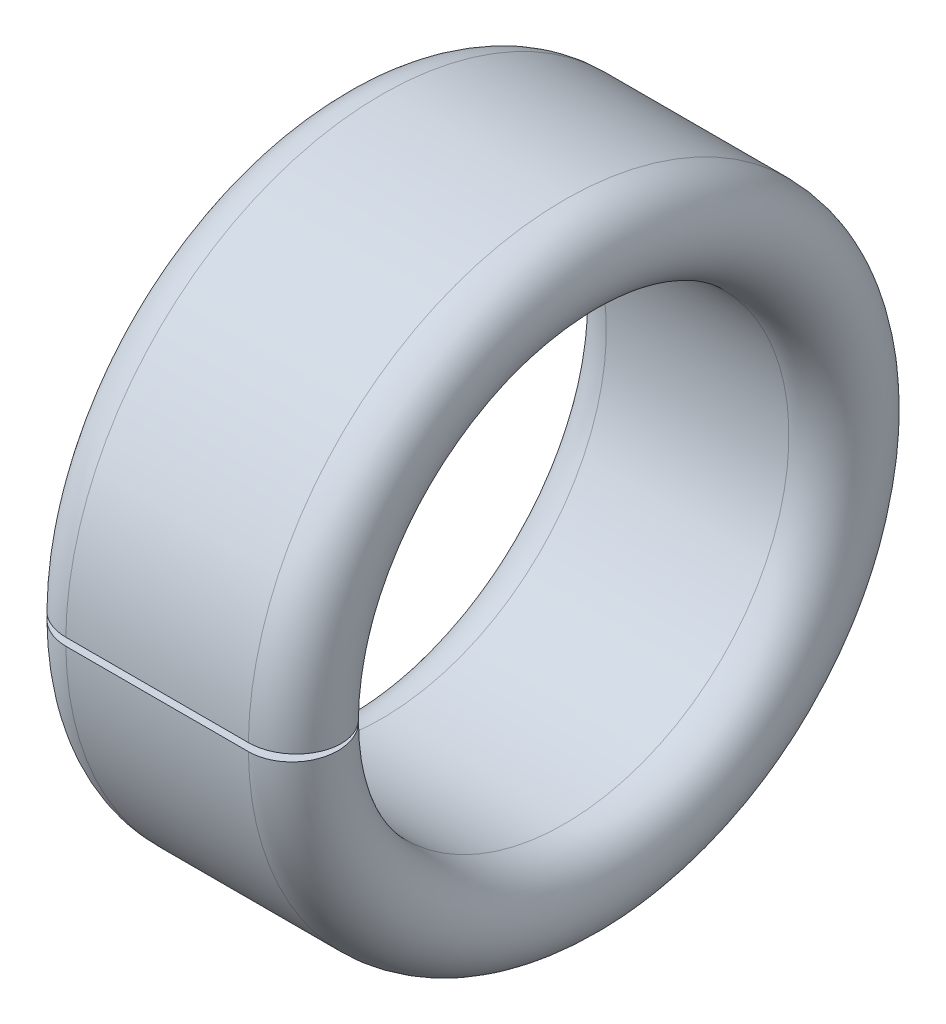
SolidWorks part; units mm, degrees
ref_plane "Front Plane" through (0, 0, 0) normal (0, 0, 1) x (1, 0, 0)
ref_plane "Top Plane" through (0, 0, 0) normal (0, 1, 0) x (1, 0, 0)
ref_plane "Right Plane" through (0, 0, 0) normal (1, 0, 0) x (0, 0, -1)
sketch "Sketch1" plane through (0, 0, 0) normal (0, 0, 1) x (1, 0, 0)
  line L0 (0.65, 3.2) -> (3.25, 3.2)
  line L1 (3.25, 4.5) -> (0.65, 4.5)
  line L2 (3.9, 0) -> (0, 0) construction
  arc A0 (0.65, 4.5) -> (0.65, 3.2) centre (0.65, 3.85) ccw
  arc A1 (3.25, 3.2) -> (3.25, 4.5) centre (3.25, 3.85) ccw
revolve "Revolve1" add sketch "Sketch1" angle 360 about L2
ref_plane "Plane1" through (3.9, 0, 0) normal (1, 0, 0) x (0, 0, -1)
sketch "Sketch2" plane through (0, 0, 0) normal (1, 0, 0) x (0, 0, -1)
  line L0 (-5.4993, -0.0903) -> (-2.9136, 0)
  line L1 (-2.9136, 0) -> (-5.4993, 0.0903)
  arc A0 (-5.4993, 0.0903) -> (-5.4993, -0.0903) centre (0, 0) ccw
extrude "Cut-Extrude1" cut sketch "Sketch2" along normal blind 3.9
ref_plane "ANBAU XY" through (0, 0, 0) normal (1, 0, 0) x (0, 0, -1)
ref_plane "ANBAU XZ" through (0, 0, 0) normal (0, -1, 0) x (-1, 0, 0)
ref_plane "ANBAU YZ" through (0, 0, 0) normal (0, 0, -1) x (-1, 0, 0)
ref_axis "ANBAU X" through (0, 0, 80.9) along (0, 0, -1)
ref_axis "ANBAU Y" through (0, -50, 0) along (0, 1, 0)
ref_axis "ANBAU Z" through (80.9, 0, 0) along (-1, 0, 0)
sketch3d "ANBAU"
  point P0 (0, 0, 0)
ref_plane "insert XY" through (0, 0, 0) normal (1, 0, 0) x (0, 0, -1)
ref_plane "insert XZ" through (0, 0, 0) normal (0, -1, 0) x (-1, 0, 0)
ref_plane "insert YZ" through (0, 0, 0) normal (0, 0, -1) x (-1, 0, 0)
ref_axis "insert X" through (0, 0, 80.9) along (0, 0, -1)
ref_axis "insert Y" through (0, -50, 0) along (0, 1, 0)
ref_axis "insert Z" through (80.9, 0, 0) along (-1, 0, 0)
sketch3d "insert"
  point P0 (0, 0, 0)
ref_plane "schraube_punkt XY" through (3.9, 0, 0) normal (1, 0, 0) x (0, 0, -1)
ref_plane "schraube_punkt XZ" through (0, 0, 0) normal (0, -1, 0) x (-1, 0, 0)
ref_plane "schraube_punkt YZ" through (0, 0, 0) normal (0, 0, -1) x (-1, 0, 0)
ref_axis "schraube_punkt X" through (3.9, 0, 80.9) along (0, 0, -1)
ref_axis "schraube_punkt Y" through (3.9, -50, 0) along (0, 1, 0)
ref_axis "schraube_punkt Z" through (80.9, 0, 0) along (-1, 0, 0)
sketch3d "schraube_punkt"
  point P0 (3.9, 0, 0)
other "Freeze***"
